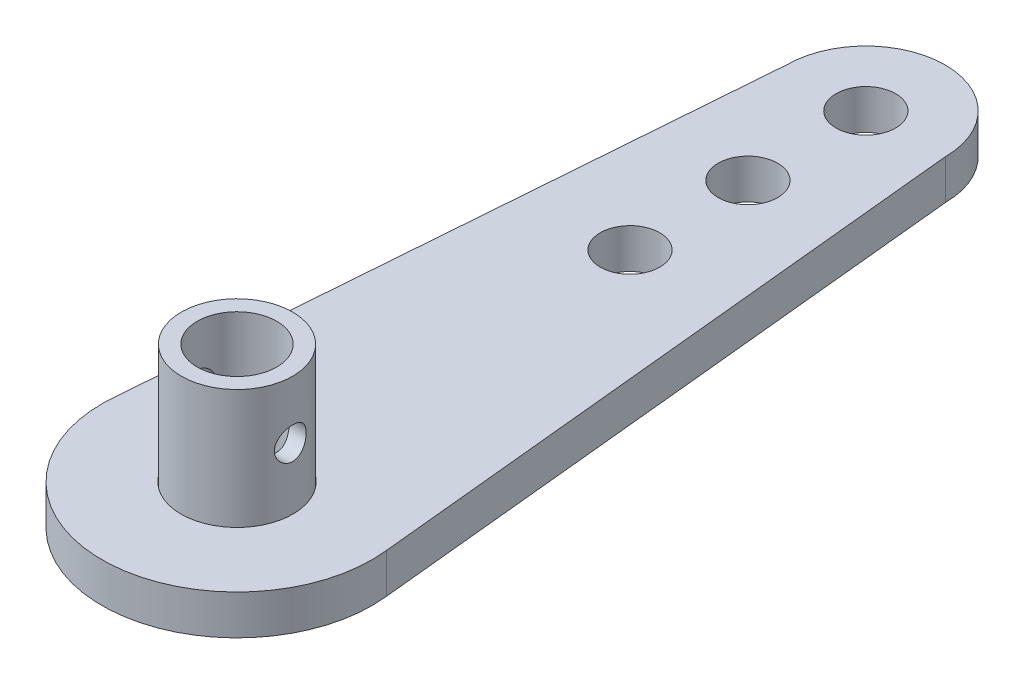
SolidWorks part; units mm, degrees
ref_plane "Front Plane" through (0, 0, 0) normal (0, 0, 1) x (1, 0, 0)
ref_plane "Top Plane" through (0, 0, 0) normal (0, 1, 0) x (1, 0, 0)
ref_plane "Right Plane" through (0, 0, 0) normal (1, 0, 0) x (0, 0, -1)
sketch "Sketch1" plane through (0, 0, 0) normal (0, 1, 0) x (1, 0, 0)
  line L0 (0, 0) -> (-1.7091, 159.9909) construction
  line L1 (-21.7091, 159.9909) -> (-33.7875, 3.7953)
  line L2 (18.2909, 159.9909) -> (33.7875, 3.7953)
  arc A0 (-33.7875, 3.7953) -> (33.7875, 3.7953) centre (0, 0) ccw
  arc A2 (18.2909, 159.9909) -> (-21.7091, 159.9909) centre (-1.7091, 159.9909) ccw
  circle A3 centre (0, 0) radius 14.1
  circle A4 centre (-1.7091, 159.9909) radius 7.5
  circle A5 centre (-1.3886, 129.9926) radius 7.5
  circle A6 centre (-1.0682, 99.9943) radius 7.5
  dimension "D1" = 3
base flange "Base-Flange1" sketch "Sketch1" thickness 10 reverse thickness direction no parameters "D1"=0.7366
sketch "Sketch6" plane through (0, 0, 0) normal (0, 1, 0) x (1, 0, 0)
  circle A0 centre (0, 0) radius 14
  circle A1 centre (0, 0) radius 10
extrude "Boss-Extrude1" add sketch "Sketch6" along normal blind 30 and the other way up to surface (10 mm away) other way up to face at (-1.0682, -10, -92.4943)
sketch "Sketch8" plane through (0, 0, 0) normal (1, 0, 0) x (0, 0, -1)
  line L0 (0, 0) -> (0, 15.4) construction
  circle A0 centre (0, 15.4) radius 4
extrude "Cut-Extrude1" cut sketch "Sketch8" against normal through all both and the other way through all
sketch "Bend-Lines1" [suppressed] plane through (0, 0, 0) normal (0, 1, 0) x (1, 0, 0)
sketch "Bounding-Box1" [suppressed] plane through (0, 0, 0) normal (0, 1, 0) x (1, 0, 0)
sheet metal parameters "Sheet-Metal1" thickness 10 parameters "D1"=0.7366
flat pattern "Flat-Pattern1" [suppressed]
sketch "Bend-Lines2" plane through (0, 0, 0) normal (0, 1, 0) x (1, 0, 0)
sketch3d "Bounding-Box2" [suppressed]
  line L0 (47.686, 176.2427, 0) -> (31.2864, -36.5125, 0) construction
  line L1 (-20.1128, 181.4688, 0) -> (-36.5125, -31.2864, 0) construction
  line L2 (47.686, 176.2427, 0) -> (-20.1128, 181.4688, 0) construction
  line L3 (31.2864, -36.5125, 0) -> (-36.5125, -31.2864, 0) construction
sheet metal parameters "Sheet-Metal2" thickness 10 parameters "D1"=0.7366
flat pattern "Flat-Pattern1"
sketch "Bend-Lines2" plane through (0, 0, 0) normal (0, 1, 0) x (1, 0, 0)
sketch3d "Bounding-Box2" [suppressed]
  line L0 (-43.029, 166.8387, 0) -> (-27.5905, -32.2298, 0) construction
  line L1 (16.7914, 171.478, 0) -> (32.2298, -27.5906, 0) construction
  line L2 (-43.029, 166.8387, 0) -> (16.7914, 171.478, 0) construction
  line L3 (-27.5905, -32.2298, 0) -> (32.2298, -27.5906, 0) construction
